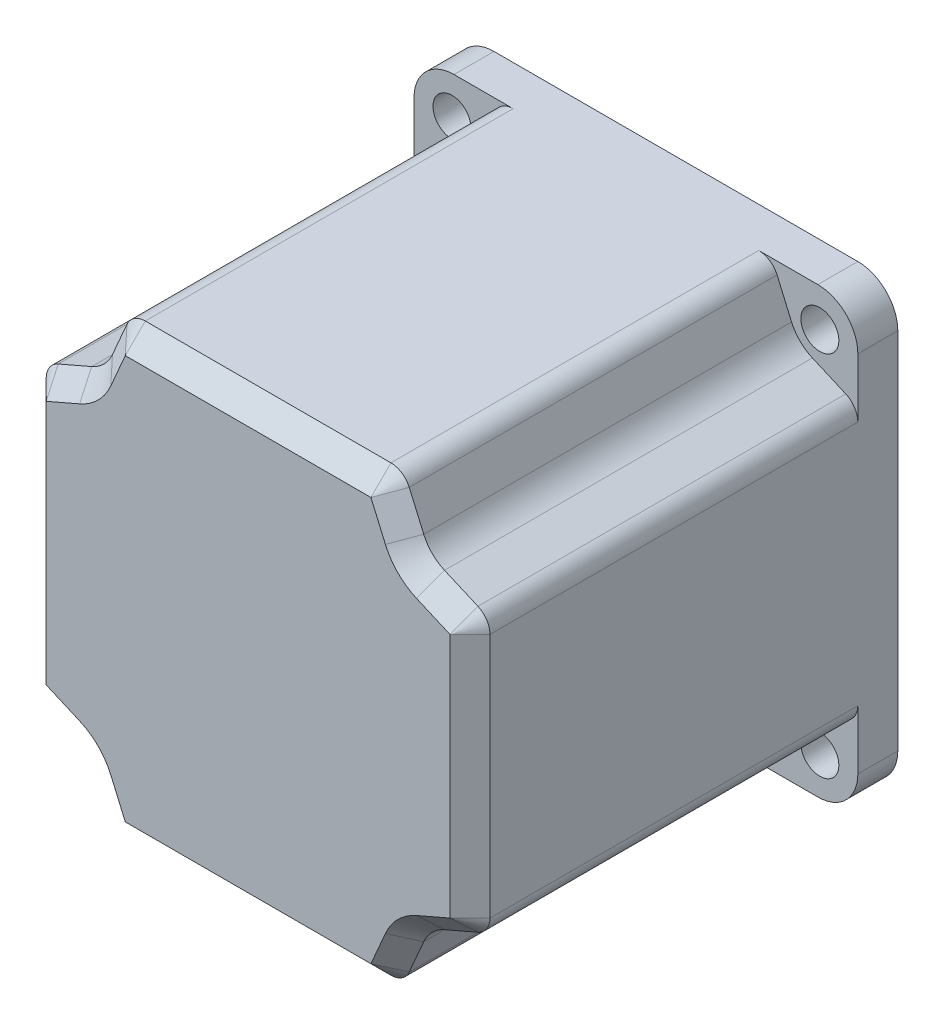
SolidWorks part; units mm, degrees
material "AISI Type A2 Tool Steel"
ref_plane "Front Plane" through (0, 0, 0) normal (0, 0, 1) x (1, 0, 0)
ref_plane "Top Plane" through (0, 0, 0) normal (0, 1, 0) x (1, 0, 0)
ref_plane "Right Plane" through (0, 0, 0) normal (1, 0, 0) x (0, 0, -1)
sketch "Sketch1" plane through (0, 0, 0) normal (0, 0, 1) x (1, 0, 0)
  line L1 (0, 0) -> (56.388, 0)
  line L2 (0, 0) -> (0, -56.388)
  line L3 (0, -56.388) -> (56.388, -56.388)
  line L4 (56.388, 0) -> (56.388, -56.388)
  dimension "D1" = 56.388
extrude "Boss-Extrude1" add sketch "Sketch1" along normal blind 54.356
sketch "Sketch3" plane through (0, 0, 54.356) normal (0, 0, 1) x (1, 0, 0)
  line L0 (0, 0) -> (10.922, 0)
  line L1 (56.388, 0) -> (0, 0) construction
  line L2 (10.922, 0) -> (7.62, -7.62)
  line L3 (7.62, -7.62) -> (0, -10.922)
  line L4 (0, 0) -> (0, -56.388) construction
  line L5 (0, -10.922) -> (0, 0)
  line L6 (56.388, 0) -> (56.388, -10.922)
  line L7 (56.388, -56.388) -> (56.388, 0) construction
  line L8 (56.388, -10.922) -> (48.768, -7.62)
  line L9 (48.768, -7.62) -> (45.466, 0)
  line L10 (45.466, 0) -> (56.388, 0)
  line L11 (0, -56.388) -> (10.922, -56.388)
  line L12 (0, -56.388) -> (56.388, -56.388) construction
  line L13 (10.922, -56.388) -> (7.62, -48.768)
  line L14 (7.62, -48.768) -> (0, -45.466)
  line L15 (0, -45.466) -> (0, -56.388)
  line L16 (56.388, -56.388) -> (56.388, -45.466)
  line L17 (56.388, -45.466) -> (48.768, -48.768)
  line L18 (48.768, -48.768) -> (45.466, -56.388)
  line L19 (45.466, -56.388) -> (56.388, -56.388)
  dimension "D1" = 10.922
  dimension "D2" = 7.62
extrude "Cut-Extrude1" cut sketch "Sketch3" along direction (0, 0, 1) on the side against the normal blind 49.276
fillet "Fillet2" radius 5.08 8 edges at (0, 0, 2.54) (56.388, 0, 2.54) (56.388, -56.388, 2.54) (0, -56.388, 2.54) (7.62, -48.768, 29.718) (48.768, -48.768, 29.718) (48.768, -7.62, 29.718) (7.62, -7.62, 29.718)
fillet "Fillet3" radius 2.54 8 edges at (45.466, 0, 29.718) (56.388, -10.922, 29.718) (56.388, -45.466, 29.718) (45.466, -56.388, 29.718) (10.922, -56.388, 29.718) (0, -45.466, 29.718) (10.922, 0, 29.718) (0, -10.922, 29.718)
sketch "Sketch6" plane through (0, 0, 0) normal (0, 0, -1) x (-1, 0, 0)
  line L4 (-28.194, 0) -> (-28.194, -56.388) construction
  line L5 (-51.308, 0) -> (-5.08, 0) construction
  line L6 (-5.08, -56.388) -> (-51.308, -56.388) construction
  circle A0 centre (-28.194, -28.194) radius 19.05
  point P16 (-28.194, -28.194)
  dimension "D1" = 38.1
extrude "Boss-Extrude2" add sketch "Sketch6" along normal blind 1.524
sketch "Sketch8" plane through (0, 0, -1.524) normal (0, 0, -1) x (-1, 0, 0)
  line L0 (-28.194, 0) -> (-28.194, -56.388) construction
  line L1 (-51.308, 0) -> (-5.08, 0) construction
  line L2 (-5.08, -56.388) -> (-51.308, -56.388) construction
  line L3 (-30.861, -26.4713) -> (-30.861, -29.9167)
  line L4 (-30.861, -28.194) -> (-25.019, -28.194) construction
  arc A0 (-30.861, -29.9167) -> (-30.861, -26.4713) centre (-28.194, -28.194) ccw
  point P10 (-28.194, -28.194)
  dimension "D1" = 6.35
  dimension "D2" = 5.842
extrude "Boss-Extrude3" add sketch "Sketch8" along normal blind 18.542
sketch "Sketch10" plane through (0, 0, 0) normal (0, 0, -1) x (-1, 0, 0)
  line L1 (-56.388, -4.826) -> (-51.562, -4.826) construction
  line L5 (-56.388, -51.308) -> (-56.388, -5.08) construction
  line L6 (-51.562, -4.826) -> (-51.562, 0) construction
  line L7 (-51.308, 0) -> (-5.08, 0) construction
  line L8 (-4.826, 0) -> (-4.826, -4.826) construction
  line L9 (-4.826, -4.826) -> (0, -4.826) construction
  line L10 (0, -5.08) -> (0, -51.308) construction
  line L11 (-56.388, -51.562) -> (-51.562, -51.562) construction
  line L12 (-51.562, -51.562) -> (-51.562, -56.388) construction
  line L13 (-5.08, -56.388) -> (-51.308, -56.388) construction
  line L14 (-4.826, -56.388) -> (-4.826, -51.562) construction
  line L15 (-4.826, -51.562) -> (0, -51.562) construction
  circle A0 centre (-51.562, -4.826) radius 2.413
  circle A2 centre (-4.826, -4.826) radius 2.413
  circle A3 centre (-51.562, -51.562) radius 2.413
  circle A4 centre (-4.826, -51.562) radius 2.413
  dimension "D3" = 4.826
  dimension "D1" = 4.826
extrude "Cut-Extrude2" cut sketch "Sketch10" against normal blind 18.542
chamfer "Chamfer1" distance 0.508 angle 45 4 edges at (49.149, -51.562, 0) (2.413, -51.562, 0) (2.413, -4.826, 0) (49.149, -4.826, 0)
chamfer "Chamfer2" distance 0.508 angle 45 1 edges at (25.019, -28.194, -20.066)
chamfer "Chamfer3" distance 2.54 angle 45 24 edges at (47.0492, -52.7344, 54.356) (45.1924, -55.9713, 54.356) (49.0385, -49.0385, 54.356) (28.194, -56.388, 54.356) (52.7344, -47.0492, 54.356) (11.1956, -55.9713, 54.356) (55.9713, -45.1924, 54.356) (9.3388, -52.7344, 54.356) (56.388, -28.194, 54.356) (7.3495, -49.0385, 54.356) (55.9713, -11.1956, 54.356) (3.6536, -47.0492, 54.356) (52.7344, -9.3388, 54.356) (0.4167, -45.1924, 54.356) (49.0385, -7.3495, 54.356) (0, -28.194, 54.356) (47.0492, -3.6536, 54.356) (0.4167, -11.1956, 54.356) (45.1924, -0.4167, 54.356) (3.6536, -9.3388, 54.356) (28.194, 0, 54.356) (7.3495, -7.3495, 54.356) (11.1956, -0.4167, 54.356) (9.3388, -3.6536, 54.356)
equation "\"glass pane length\"= 14.125"
equation "\"glass pane width\"= 10.1875"
equation "\"glass pane wall width\"= 3/4"
equation "\"glass lip\"= 1/4"
equation "\"bolt diameter\"= 0.2"
equation "\"stepper mount offset\"= 0.19"
equation "\"stepper mount diameter\"= 0.19"
equation "\"D3@Sketch10\"=\"stepper mount diameter\""
equation "\"D1@Sketch10\"=\"stepper mount offset\""
equation "\"stepper body width\"= 2.22"
equation "\"D1@Sketch1\"=\"stepper body width\""
